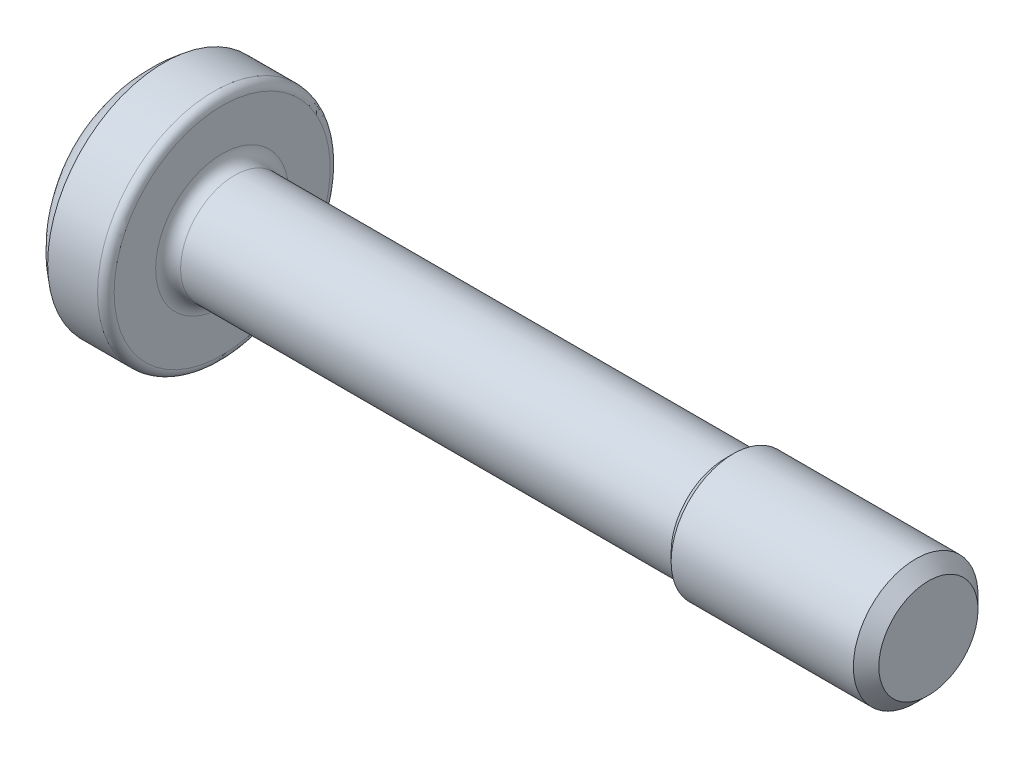
SolidWorks part; units mm, degrees
ref_plane "Ebene vorne" through (0, 0, 0) normal (0, 0, 1) x (1, 0, 0)
ref_plane "Ebene oben" through (0, 0, 0) normal (0, 1, 0) x (1, 0, 0)
ref_plane "Ebene rechts" through (0, 0, 0) normal (1, 0, 0) x (0, 0, -1)
sketch "Skizze1" plane through (0, 0, 0) normal (0, 0, 1) x (1, 0, 0)
  line L0 (-2.4, 0) -> (-2.4, 1.4)
  line L1 (-1.4, 2.8) -> (-0.2, 2.8)
  line L2 (0, 2.6) -> (0, 1.6)
  line L3 (0.3, 1.3) -> (12.1065, 1.3)
  line L4 (12.1065, 1.3) -> (12.3065, 1.5)
  line L5 (12.3065, 1.5) -> (16.6935, 1.5)
  line L6 (16.6935, 1.5) -> (17, 1.1935)
  line L7 (17, 1.1935) -> (17, 0)
  line L8 (17, 0) -> (-2.4, 0)
  line L9 (17, 0) -> (-2.4, 0) construction
  arc A0 (-2.4, 1.4) -> (-1.4, 2.8) centre (0.2683, 0.5512) cw
  arc A1 (-0.2, 2.8) -> (0, 2.6) centre (-0.2, 2.6) cw
  arc A2 (0, 1.6) -> (0.3, 1.3) centre (0.3, 1.6) ccw
revolve "Rotation1" add sketch "Skizze1" angle 360 about L9 reverse direction yes
cosmetic thread "Gewindedarstellung1" parameters "D1"=4.8935, "D2"=2.387
ref_plane "Ebene1" through (-2.4, 0, 0) normal (-1, 0, 0) x (0, 0, 1)
sketch "Skizze2" plane through (-2.4, 0, 0) normal (-1, 0, 0) x (0, 0, 1)
  line L0 (0.38, -2.0145) -> (0.38, -0.9755)
  line L1 (0.38, 0.9755) -> (0.38, 2.0145)
  line L2 (-0.38, 2.0145) -> (-0.38, 0.9755)
  line L3 (-0.38, -0.9755) -> (-0.38, -2.0145)
  arc A0 (-0.38, -2.0145) -> (0.38, -2.0145) centre (0, 0) ccw
  arc A1 (0.38, -0.9755) -> (0.8897, -0.8282) centre (0.7492, -1.2977) cw
  arc A2 (0.8897, -0.8282) -> (1.1621, -0.3564) centre (0.9699, -0.56) ccw
  arc A3 (1.1621, -0.3564) -> (1.1621, 0.3564) centre (1.4984, 0) cw
  arc A4 (1.1621, 0.3564) -> (0.8897, 0.8282) centre (0.9699, 0.56) ccw
  arc A5 (0.8897, 0.8282) -> (0.38, 0.9755) centre (0.7492, 1.2977) cw
  arc A6 (0.38, 2.0145) -> (-0.38, 2.0145) centre (0, 0) ccw
  arc A7 (-0.38, 0.9755) -> (-0.8897, 0.8282) centre (-0.7492, 1.2977) cw
  arc A8 (-0.8897, 0.8282) -> (-1.1621, 0.3564) centre (-0.9699, 0.56) ccw
  arc A9 (-1.1621, 0.3564) -> (-1.1621, -0.3564) centre (-1.4984, 0) cw
  arc A10 (-1.1621, -0.3564) -> (-0.8897, -0.8282) centre (-0.9699, -0.56) ccw
  arc A11 (-0.8897, -0.8282) -> (-0.38, -0.9755) centre (-0.7492, -1.2977) cw
extrude "Schnitt-Linear austragen1" cut sketch "Skizze2" against normal blind 2.1
sketch "Skizze3" plane through (0, 0, 0) normal (0, 0, 1) x (1, 0, 0)
  line L0 (-2.4, 0) -> (-2.4, 1.4)
  line L1 (-2.4, 1.4) -> (-1, 0)
  line L2 (-1, 0) -> (-2.4, 0)
  line L3 (-1, 0) -> (-2.4, 0) construction
revolve "Schnitt-Rotation1" cut sketch "Skizze3" angle 360 about L3 reverse direction yes
ref_plane "Ebene2" through (-2.4, 0, 0) normal (1, 0, 0) x (0, 0, -1)
ref_plane "Ebene3" through (0, 0, 0) normal (1, 0, 0) x (0, 0, -1)
ref_plane "ANBAU XY" through (0, 0, 0) normal (1, 0, 0) x (0, 0, -1)
ref_plane "ANBAU XZ" through (0, 0, 0) normal (0, -1, 0) x (-1, 0, 0)
ref_plane "ANBAU YZ" through (0, 0, 0) normal (0, 0, -1) x (-1, 0, 0)
ref_axis "ANBAU X" through (0, 0, 80.9) along (0, 0, -1)
ref_axis "ANBAU Y" through (0, -50, 0) along (0, 1, 0)
ref_axis "ANBAU Z" through (80.9, 0, 0) along (-1, 0, 0)
sketch3d "ANBAU"
  point P0 (0, 0, 0)
ref_plane "MONTAGE XY" through (0, 0, 0) normal (-1, 0, 0) x (0, 0, 1)
ref_plane "MONTAGE XZ" through (0, 0, 0) normal (0, 1, 0) x (1, 0, 0)
ref_plane "MONTAGE YZ" through (0, 0, 0) normal (0, 0, -1) x (-1, 0, 0)
ref_axis "MONTAGE X" through (0, 0, 80.9) along (0, 0, -1)
ref_axis "MONTAGE Y" through (0, 50, 0) along (0, -1, 0)
ref_axis "MONTAGE Z" through (-80.9, 0, 0) along (1, 0, 0)
sketch3d "MONTAGE"
  point P0 (0, 0, 0)
